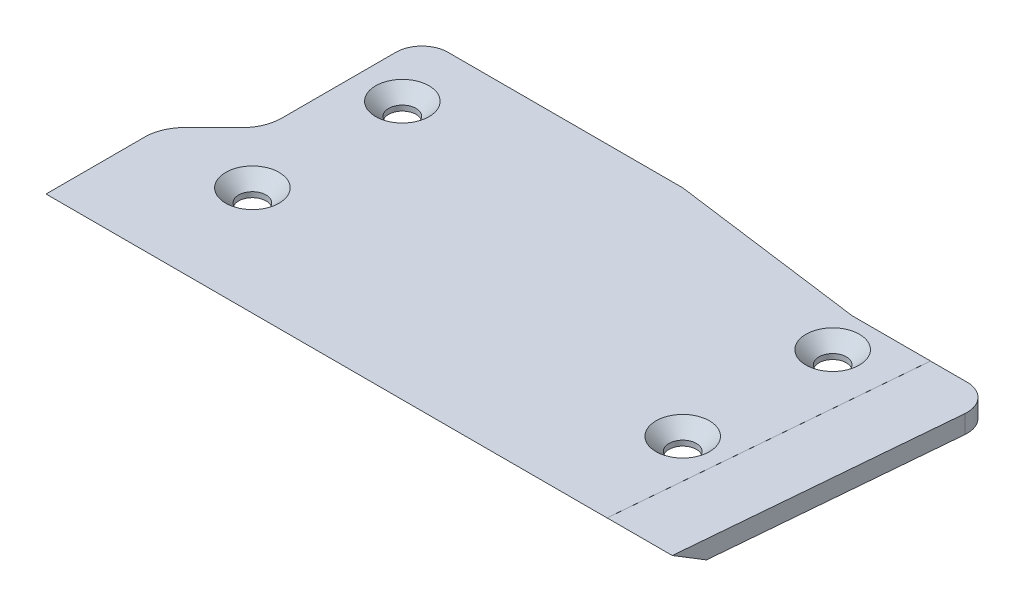
SolidWorks part; units mm, degrees
material "Titanium Ti-8Al-1Mo-1V"
ref_plane "Front Plane" through (0, 0, 0) normal (0, 0, 1) x (1, 0, 0)
ref_plane "Top Plane" through (0, 0, 0) normal (0, 1, 0) x (1, 0, 0)
ref_plane "Right Plane" through (0, 0, 0) normal (1, 0, 0) x (0, 0, -1)
sketch "Sketch1" plane through (0, 0, 0) normal (0, 1, 0) x (1, 0, 0)
  line L1 (0, 4) -> (40, 4)
  line L2 (40, 4) -> (70, 0)
  line L3 (70, 0) -> (92, 0)
  line L4 (92, 0) -> (88, -46)
  line L5 (88, -46) -> (0, -46)
  line L7 (0, -46) -> (-8, -46)
  line L8 (-8, -46) -> (-8, -28)
  line L9 (-8, -28) -> (0, -20)
  line L11 (0, 4) -> (0, -20)
  dimension "D1" = 46
  dimension "D2" = 22
  dimension "D3" = 30
  dimension "D4" = 88
  dimension "D5" = 40
  dimension "D6" = 4
  dimension "D7" = 8
  dimension "D8" = 18
  dimension "D9" = 8
extrude "Boss-Extrude1" add sketch "Sketch1" along normal blind 2.8
chamfer "Chamfer1" distance 3 angle 60 1 edges at (40, 0, 46) first distance on face at (40, 1.4, 46)
sketch "Sketch2" plane through (0, 2.8, 0) normal (0, 1, 0) x (1, 0, 0)
  line L1 (92, 0) -> (70, 0) construction
  line L2 (0, 4) -> (0, -20) construction
  circle A0 centre (7, -6) radius 2.1
  circle A1 centre (7, -29) radius 2.1
  circle A2 centre (73, -6) radius 2.1
  circle A3 centre (73, -29) radius 2.1
  dimension "D2" = 4.2
  dimension "D5" = 4.2
  dimension "D1" = 7
  dimension "D3" = 6
  dimension "D4" = 23
  dimension "D7" = 66
  dimension "D6" = 2
extrude "Cut-Extrude1" cut sketch "Sketch2" against normal through all
chamfer "Chamfer2" distance 2 angle 45 4 edges at (73, 2.8, 8.1) (73, 2.8, 31.1) (7, 2.8, 8.1) (7, 2.8, 31.1)
fillet "Fillet1" radius 6 2 edges at (0, 1.4, 20) (-8, 1.4, 28)
fillet "Fillet2" radius 4 2 edges at (0, 1.4, -4) (92, 1.4, 0)
sketch "Sketch3" plane through (0, 2.8, 0) normal (0, 1, 0) x (1, 0, 0)
  line L0 (78.0413, -45.6536) -> (82.0112, 0)
  line L1 (-8, -45.6536) -> (88.0301, -45.6536) construction
  line L2 (87.6371, 0) -> (70, 0) construction
  line L3 (78.0413, -45.6536) -> (88.0301, -45.6536)
  line L4 (88.0301, -45.6536) -> (92.3417, 0.8014)
  line L5 (92.3417, 0.8014) -> (82.0112, 0)
extrude "Cut-Extrude2" cut sketch "Sketch3" against normal blind 0.01
